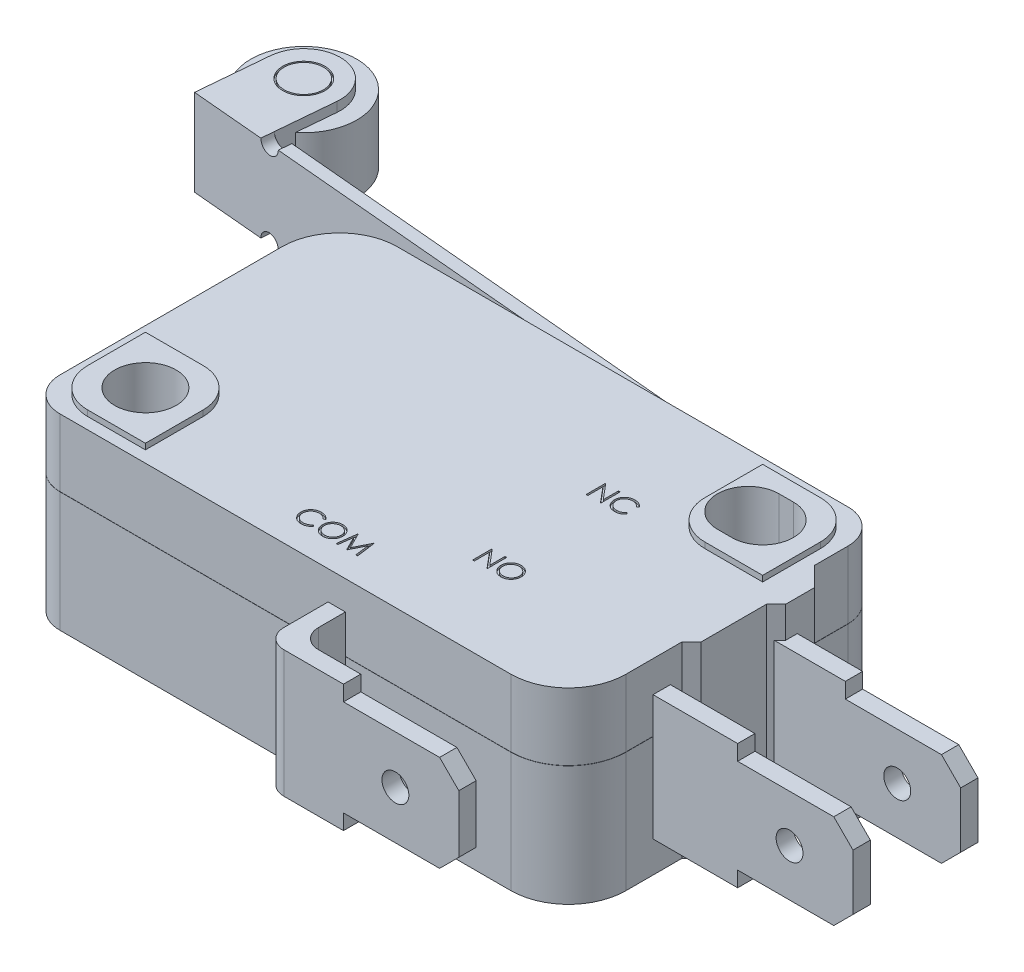
SolidWorks part; units mm, degrees
ref_plane "Front Plane" through (0, 0, 0) normal (0, 0, 1) x (1, 0, 0)
ref_plane "Top Plane" through (0, 0, 0) normal (0, 1, 0) x (1, 0, 0)
ref_plane "Right Plane" through (0, 0, 0) normal (1, 0, 0) x (0, 0, -1)
sketch "Sketch1" plane through (0, 0, 0) normal (0, 1, 0) x (1, 0, 0)
  line L1 (0, 0) -> (28.2, 0)
  line L2 (0, 0) -> (0, 16.3)
  line L3 (0, 16.3) -> (28.2, 16.3)
  line L4 (28.2, 0) -> (28.2, 16.3)
  dimension "D1" = 16.3
  dimension "D2" = 28.2
extrude "Boss-Extrude1" add sketch "Sketch1" along normal blind 9.75
fillet "Fillet1" radius 3 2 edges at (0, 4.875, -16.3) (28.2, 4.875, 0)
fillet "Fillet2" radius 1.75 2 edges at (0, 4.875, 0) (28.2, 4.875, -16.3)
sketch "Sketch2" plane through (0, 9.75, 0) normal (0, 1, 0) x (1, 0, 0)
  line L0 (26.45, 16.2) -> (3, 16.2)
  line L1 (0.1, 13.3) -> (0.1, 1.75)
  line L2 (1.75, 0.1) -> (25.2, 0.1)
  line L3 (28.1, 3) -> (28.1, 14.55)
  line L4 (26.45, 16.3) -> (3, 16.3)
  line L5 (0, 13.3) -> (0, 1.75)
  line L6 (1.75, 0) -> (25.2, 0)
  line L7 (28.2, 3) -> (28.2, 14.55)
  line L8 (26.45, 16.3) -> (3, 16.3)
  line L9 (0, 13.3) -> (0, 1.75)
  line L10 (1.75, 0) -> (25.2, 0)
  line L11 (28.2, 3) -> (28.2, 14.55)
  arc A0 (3, 16.2) -> (0.1, 13.3) centre (3, 13.3) ccw
  arc A1 (0.1, 1.75) -> (1.75, 0.1) centre (1.75, 1.75) ccw
  arc A2 (25.2, 0.1) -> (28.1, 3) centre (25.2, 3) ccw
  arc A3 (28.1, 14.55) -> (26.45, 16.2) centre (26.45, 14.55) ccw
  arc A4 (3, 16.3) -> (0, 13.3) centre (3, 13.3) ccw
  arc A6 (25.2, 0) -> (28.2, 3) centre (25.2, 3) ccw
  arc A8 (3, 16.3) -> (0, 13.3) centre (3, 13.3) ccw
  arc A10 (25.2, 0) -> (28.2, 3) centre (25.2, 3) ccw
  arc A12 (0, 1.75) -> (1.75, 0) centre (1.75, 1.75) ccw
  arc A13 (0, 1.75) -> (1.75, 0) centre (1.75, 1.75) ccw
  arc A14 (28.2, 14.55) -> (26.45, 16.3) centre (26.45, 14.55) ccw
  arc A15 (28.2, 14.55) -> (26.45, 16.3) centre (26.45, 14.55) ccw
  dimension "D1" = 0
  dimension "D2" = 0.1
extrude "Cut-Extrude1" cut sketch "Sketch2" against normal blind 0.01 from offset 3.5 offset against normal yes
sketch "Sketch3" plane through (0, 9.75, 0) normal (0, 1, 0) x (1, 0, 0)
  line L0 (1.75, 0) -> (25.2, 0) construction
  line L1 (0, 13.3) -> (0, 1.75) construction
  line L2 (26.45, 16.3) -> (3, 16.3) construction
  line L3 (28.2, 3) -> (28.2, 14.55) construction
  circle A0 centre (3.1, 3.1) radius 1.6
  circle A1 centre (25.1, 13.2) radius 1.6
  point P4 (26.7, 13.2)
  point P5 (25.1, 14.8)
  point P6 (3.1, 1.5)
  point P7 (1.5, 3.1)
  dimension "D1" = 3.2
  dimension "D2" = 1.5
  dimension "D3" = 1.5
  dimension "D4" = 1.5
  dimension "D5" = 1.5
extrude "Cut-Extrude2" cut sketch "Sketch3" against normal through all
sketch "Sketch4" plane through (0, 9.75, 0) normal (0, 1, 0) x (1, 0, 0)
  line L0 (5.6, 3.1) -> (0.6, 3.1) construction
  line L1 (0.6, 5.6) -> (3.6, 5.6)
  line L2 (0.6, 5.6) -> (0.6, 2.6)
  line L3 (2.6, 0.6) -> (5.6, 0.6)
  line L4 (5.6, 3.6) -> (5.6, 0.6)
  line L5 (3.1, 0.6) -> (3.1, 5.6) construction
  arc A0 (0.6, 2.6) -> (2.6, 0.6) centre (2.6, 2.6) ccw
  arc A1 (3.6, 5.6) -> (5.6, 3.6) centre (3.6, 3.6) cw
  circle A2 centre (3.1, 3.1) radius 1.6 construction
  circle A3 centre (3.1, 3.1) radius 1.6
  point P11 (3.1, 3.1)
  point P15 (3.1, 3.1)
  dimension "D1" = 2
  dimension "D2" = 5
  dimension "D3" = 5
extrude "Boss-Extrude2" add sketch "Sketch4" along normal blind 0.3
sketch "Sketch5" plane through (0, 9.75, 0) normal (0, 1, 0) x (1, 0, 0)
  line L2 (0, 8.15) -> (28.2, 8.15) construction
  line L3 (0, 13.3) -> (0, 1.75) construction
  line L4 (28.2, 3) -> (28.2, 14.55) construction
  line L5 (14.1, 0) -> (14.1, 16.3) construction
  line L6 (1.75, 0) -> (25.2, 0) construction
  line L7 (26.45, 16.3) -> (3, 16.3) construction
  circle A0 centre (14.1, 8.15) radius 2.5
  point P14 (14.1, 8.15)
  point P16 (14.1, 8.15)
  dimension "D1" = 5
extrude "Cut-Extrude3" cut sketch "Sketch5" against normal blind 0.1
pattern_circular "CirPattern1" count 2 over 360 about axis through (14.1, 9.75, -8.15) along (0, 1, 0) of "Boss-Extrude2"
sketch "Sketch6" plane through (0, 9.75, 0) normal (0, 1, 0) x (1, 0, 0)
  circle A0 centre (14.1, 8.15) radius 2.5
  circle A1 centre (14.1, 8.15) radius 2.5 construction
extrude "Boss-Extrude3" add sketch "Sketch6" against normal up to surface (0.1 mm away) up to face at (14.1, 9.65, -5.65)
ref_plane "Plane1" through (0, 4.875, 0) normal (0, -1, 0) x (-1, 0, 0)
mirror "Mirror1" about plane through (0, 4.875, 0) normal (0, -1, 0) of "CirPattern1"
sketch "Sketch8" plane through (0, 9.75, 0) normal (0, 1, 0) x (1, 0, 0)
  line L1 (28.2, 5.9) -> (28.2, 12.8)
  line L2 (28.2, 3) -> (28.2, 14.55) construction
  line L3 (28.2, 12.8) -> (29.2, 11.8)
  line L4 (29.2, 11.8) -> (29.2, 10.3)
  line L5 (29.2, 10.3) -> (28.7, 9.8)
  line L6 (28.7, 9.8) -> (28.7, 6.4)
  line L7 (28.7, 6.4) -> (28.2, 5.9)
  line L8 (26.45, 16.3) -> (3, 16.3) construction
  dimension "D1" = 1
  dimension "D2" = 0.5
  dimension "D3" = 6.9
  dimension "D4" = 3
  dimension "D5" = 45
  dimension "D6" = 45
  dimension "D7" = 45
  dimension "D8" = 3.5
extrude "Boss-Extrude4" add sketch "Sketch8" against normal up to surface (9.75 mm away) up to face at (25.1, 0, -13.2)
sketch "Sketch9" plane through (28.2, 0, 0) normal (1, 0, 0) x (0, 0, -1)
  line L1 (4.4, 8.125) -> (5.3, 8.125)
  line L2 (4.4, 8.125) -> (4.4, 1.625)
  line L3 (4.4, 1.625) -> (5.3, 1.625)
  line L4 (5.3, 8.125) -> (5.3, 1.625)
  line L5 (10, 8.125) -> (10.9, 8.125)
  line L6 (10, 8.125) -> (10, 1.625)
  line L7 (10, 1.625) -> (10.9, 1.625)
  line L8 (10.9, 8.125) -> (10.9, 1.625)
  line L11 (6.4, 0) -> (6.4, 9.75) construction
  line L12 (16.3, 9.75) -> (16.3, 6.25) construction
  point P10 (4.4, 4.875)
  point P11 (6.4, 4.875)
  point P12 (10, 4.875)
  dimension "D1" = 0.9
  dimension "D2" = 6.5
  dimension "D3" = 5.4
  dimension "D4" = 6.5
extrude "Boss-Extrude5" add sketch "Sketch9" along normal blind 4.4
sketch "Sketch10" plane through (32.6, 0, 0) normal (1, 0, 0) x (0, 0, -1)
  line L0 (4.4, 8.125) -> (4.4, 1.625) construction
  line L1 (4.4, 7.325) -> (5.3, 7.325)
  line L2 (4.4, 7.325) -> (4.4, 2.425)
  line L3 (4.4, 2.425) -> (5.3, 2.425)
  line L4 (5.3, 7.325) -> (5.3, 2.425)
  line L5 (5.3, 1.625) -> (5.3, 8.125) construction
  line L6 (10, 1.625) -> (10, 8.125) construction
  line L7 (10, 7.325) -> (10.9, 7.325)
  line L8 (10, 7.325) -> (10, 2.425)
  line L9 (10, 2.425) -> (10.9, 2.425)
  line L10 (10.9, 7.325) -> (10.9, 2.425)
  line L11 (10.9, 1.625) -> (10.9, 8.125) construction
  line L12 (6.4, 0) -> (6.4, 9.75) construction
  point P16 (4.4, 4.875)
  point P19 (6.4, 4.875)
  dimension "D1" = 4.9
extrude "Boss-Extrude6" add sketch "Sketch10" along normal blind 6
chamfer "Chamfer1" distance 1 angle 45 4 edges at (38.6, 2.425, -10.45) (38.6, 7.325, -10.45) (38.6, 2.425, -4.85) (38.6, 7.325, -4.85)
sketch "Sketch11" plane through (0, 0, -4.4) normal (0, 0, 1) x (1, 0, 0)
  line L0 (38.6, 6.325) -> (38.6, 3.425) construction
  circle A0 centre (35.3, 4.875) radius 0.7
  point P4 (38.6, 4.875)
  point P5 (36, 4.875)
  point P6 (38.6, 4.875)
  dimension "D1" = 1.4
  dimension "D2" = 2.6
extrude "Cut-Extrude4" cut sketch "Sketch11" against normal through all
sketch "Sketch12" plane through (0, 10.05, 0) normal (0, 1, 0) x (1, 0, 0)
  line L0 (25.1, 13.2) -> (24.35, 13.2) construction
  line L1 (25.1, 11.6) -> (24.35, 11.6)
  line L2 (25.1, 14.8) -> (24.35, 14.8)
  arc A0 (25.1, 11.6) -> (25.1, 14.8) centre (25.1, 13.2) ccw
  arc A1 (24.35, 14.8) -> (24.35, 11.6) centre (24.35, 13.2) ccw
  circle A2 centre (25.1, 13.2) radius 1.6 construction
  point P3 (24.725, 13.2)
  dimension "D1" = 0.75
extrude "Cut-Extrude5" cut sketch "Sketch12" against normal through all
sketch "Sketch13" plane through (0, 9.75, 0) normal (0, 1, 0) x (1, 0, 0)
  line L0 (15.7, 0) -> (15.7, -2.3)
  line L1 (1.75, 0) -> (25.2, 0) construction
  line L2 (16.7, -3.3) -> (25.8, -3.3)
  line L3 (25.8, -3.3) -> (25.8, -2.4)
  line L4 (25.8, -2.4) -> (17.6, -2.4)
  line L5 (16.6, -1.4) -> (16.6, 0)
  line L6 (16.6, 0) -> (15.7, 0)
  line L7 (28.2, 3) -> (28.2, 5.9) construction
  arc A0 (15.7, -2.3) -> (16.7, -3.3) centre (16.7, -2.3) ccw
  arc A1 (17.6, -2.4) -> (16.6, -1.4) centre (17.6, -1.4) cw
  dimension "D1" = 1
  dimension "D2" = 3.3
  dimension "D3" = 0.9
  dimension "D4" = 10.1
  dimension "D5" = 2.4
extrude "Boss-Extrude7" add sketch "Sketch13" against normal blind 6.6 from offset 1.5 offset against normal yes
sketch "Sketch14" plane through (0, 0, 3.3) normal (0, 0, 1) x (1, 0, 0)
  line L0 (19.8, 8.25) -> (19.8, 7.45)
  line L1 (16.7, 8.25) -> (25.8, 8.25) construction
  line L2 (19.8, 7.45) -> (24.8, 7.45)
  line L3 (24.8, 7.45) -> (25.8, 6.45)
  line L4 (25.8, 1.65) -> (25.8, 8.25) construction
  line L5 (25.8, 6.45) -> (25.8, 8.25)
  line L6 (25.8, 3.45) -> (24.8, 2.45)
  line L7 (24.8, 2.45) -> (19.8, 2.45)
  line L8 (19.8, 2.45) -> (19.8, 1.65)
  line L9 (16.7, 1.65) -> (25.8, 1.65) construction
  line L10 (19.8, 1.65) -> (25.8, 1.65)
  line L11 (25.8, 1.65) -> (25.8, 3.45)
  line L12 (25.8, 8.25) -> (19.8, 8.25)
  dimension "D1" = 6
  dimension "D2" = 1
  dimension "D3" = 5
extrude "Cut-Extrude6" cut sketch "Sketch14" against normal up to next
sketch "Sketch15" plane through (0, 0, 3.3) normal (0, 0, 1) x (1, 0, 0)
  line L0 (25.8, 3.45) -> (25.8, 6.45) construction
  circle A0 centre (22.5, 4.95) radius 0.7
  circle A1 centre (35.3, 4.875) radius 0.7 construction
  point P6 (25.8, 4.95)
  point P7 (23.2, 4.95)
  dimension "D1" = 2.6
extrude "Cut-Extrude7" cut sketch "Sketch15" against normal up to next
sketch "Sketch16" plane through (0, 0, -16.3) normal (0, 0, -1) x (-1, 0, 0)
  line L0 (0, 6.24) -> (0, 0) construction
  line L1 (-7, 6.875) -> (-4, 6.875)
  line L2 (-7, 6.875) -> (-7, 2.875)
  line L3 (-7, 2.875) -> (-4, 2.875)
  line L4 (-4, 6.875) -> (-4, 2.875)
  line L5 (-38.6, 3.425) -> (-38.6, 6.325) construction
  point P8 (-38.6, 4.875)
  point P9 (-7, 4.875)
  dimension "D1" = 3
  dimension "D2" = 4
  dimension "D3" = 4
extrude "Boss-Extrude8" add sketch "Sketch16" along normal blind 2.75
fillet "Fillet3" radius 1.5 2 edges at (7, 4.875, -19.05) (4, 4.875, -19.05)
sketch "Sketch17" plane through (0, 4.875, 0) normal (0, -1, 0) x (-1, 0, 0)
  line L0 (-16.2, 16.3) -> (-16.2, 17.8444)
  line L1 (-26.45, 16.3) -> (-3, 16.3) construction
  line L2 (-15.2887, 18.8405) -> (11.7932, 21.2532)
  line L3 (11.7932, 21.2532) -> (11.8509, 20.6058)
  line L4 (11.8509, 20.6058) -> (-14.6387, 18.2458)
  line L5 (-15.55, 17.2498) -> (-15.55, 16.3)
  line L6 (-15.55, 16.3) -> (-16.2, 16.3)
  line L7 (-28.2, 12.8) -> (-28.2, 14.55) construction
  line L8 (-4, 16.3) -> (-3, 16.3) construction
  line L9 (0, 13.3) -> (0, 1.75) construction
  arc A1 (-14.6387, 18.2458) -> (-15.55, 17.2498) centre (-14.55, 17.2498) ccw
  arc A2 (-16.2, 17.8444) -> (-15.2887, 18.8405) centre (-15.2, 17.8444) cw
  point P10 (-5.5, 19.05)
  point P11 (-5.5, 19.06)
  point P17 (0, 19.55)
  point P18 (-3.5, 16.3)
  dimension "D3" = 1
  dimension "D1" = 0.65
  dimension "D2" = 12
  dimension "D4" = 28.2
  dimension "D5" = 3.25
  dimension "D6" = 0.01
extrude "Boss-Extrude10" add sketch "Sketch17" along normal blind 2.25 and the other way blind 2.25
sketch "Sketch19" plane through (0, 7.125, 0) normal (0, 1, 0) x (1, 0, 0)
  line L1 (-11.7932, 21.2532) -> (15.2887, 18.8405) construction
  line L2 (-11.7932, 21.2532) -> (-11.527, 24.2414)
  line L3 (-8.0082, 20.916) -> (-7.742, 23.9042)
  line L4 (-8.0082, 20.916) -> (-11.7932, 21.2532)
  arc A1 (-7.742, 23.9042) -> (-11.527, 24.2414) centre (-9.6345, 24.0728) ccw
  dimension "D1" = 1.9
  dimension "D2" = 3
extrude "Boss-Extrude11" add sketch "Sketch19" against normal up to surface (4.5 mm away) up to face at (8.7713, 2.625, -18.3742)
sketch "Sketch20" plane through (1.7857, 0, -20.0435) normal (0.0887, 0, -0.9961) x (-0.9961, 0, -0.0887)
  line L0 (9.8327, 7.125) -> (-13.5565, 7.125) construction
  line L1 (9.8327, 2.625) -> (-13.5565, 2.625) construction
  circle A0 centre (9.3327, 7.125) radius 0.5
  circle A1 centre (9.3327, 2.625) radius 0.5
  point P4 (9.8327, 7.125)
  dimension "D1" = 1
extrude "Cut-Extrude8" cut sketch "Sketch20" against normal up to next
sketch "Sketch21" plane through (0, 4.875, 0) normal (0, -1, 0) x (-1, 0, 0)
  circle A0 centre (9.6345, 24.0728) radius 2.75
  arc A1 (11.527, 24.2414) -> (7.742, 23.9042) centre (9.6345, 24.0728) ccw construction
  dimension "D1" = 5.5
extrude "Boss-Extrude12" add sketch "Sketch21" along normal blind 1.75 and the other way blind 1.75
sketch "Sketch22" plane through (0, 7.125, 0) normal (0, 1, 0) x (1, 0, 0)
  circle A0 centre (-9.6345, 24.0728) radius 1.1
  circle A1 centre (-9.6345, 24.0728) radius 1.02
  dimension "D1" = 2.2
  dimension "D2" = 0.08
extrude "Cut-Extrude9" cut sketch "Sketch22" against normal blind 0.1
mirror "Mirror2" about plane through (0, 4.875, 0) normal (0, -1, 0) of "Cut-Extrude9"
sketch "Sketch23" plane through (0, 9.75, 0) normal (0, 1, 0) x (1, 0, 0)
  line L0 (18.9407, 10.0501) -> (25.2222, 10.0501) construction
  line L1 (18.9407, 4.1485) -> (26.7998, 4.1485) construction
  line L2 (12.3671, 1.3437) -> (20.46, 1.3437) construction
  text T0 "NC" font "Century Gothic" height 1
  text T1 "NO" font "Century Gothic" height 1
  text T2 "COM" font "Century Gothic" height 1
extrude "Cut-Extrude10" cut sketch "Sketch23" against normal blind 0.1
